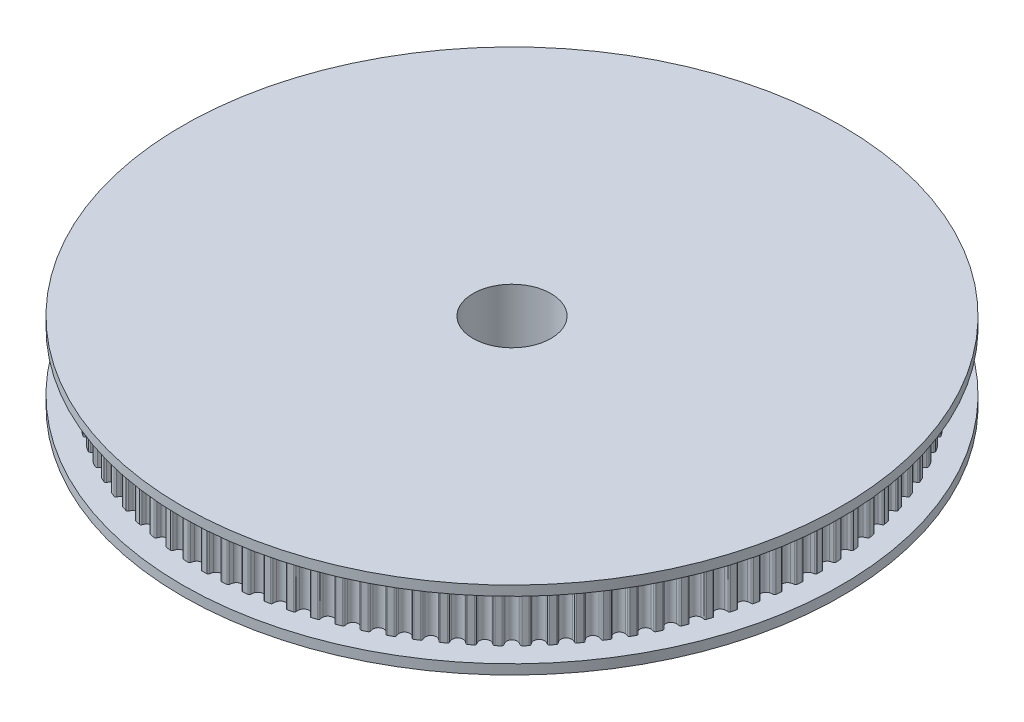
SolidWorks part; units mm, degrees
ref_plane "Front Plane" through (0, 0, 0) normal (0, 0, 1) x (1, 0, 0)
ref_plane "Top Plane" through (0, 0, 0) normal (0, 1, 0) x (1, 0, 0)
ref_plane "Right Plane" through (0, 0, 0) normal (1, 0, 0) x (0, 0, -1)
sketch "Sketch1" plane through (0, 0, 0) normal (0, 1, 0) x (1, 0, 0)
  circle A0 centre (0, 0) radius 31.831
  dimension "D1" = 63.662
extrude "Boss-Extrude1" add sketch "Sketch1" along normal mid plane 6
sketch "Sketch2" plane through (0, 0, 0) normal (0, 1, 0) x (1, 0, 0)
  line L0 (0, 0) -> (0, 31.577) construction
  line L1 (0, 0) -> (0.9857, 31.3665) construction
  line L2 (0, 31.577) -> (0, 31.831)
  line L3 (0.9857, 31.3665) -> (0.9998, 31.8153) construction
  line L4 (0.9998, 31.8153) -> (1.3996, 31.8002) construction
  line L5 (1.3996, 31.8002) -> (1.3902, 31.5521) construction
  line L6 (1.9827, 31.5147) -> (1.9987, 31.7682)
  arc A1 (0, 31.577) -> (0.2483, 31.576) centre (0, 0) cw
  arc A2 (0.2483, 31.576) -> (0.3962, 31.4425) centre (0.2471, 31.426) cw
  arc A3 (0.3962, 31.4425) -> (0.4813, 31.1351) centre (1.3902, 31.5521) ccw
  arc A4 (0.4813, 31.1351) -> (1.4746, 31.1038) centre (0.9857, 31.3665) ccw
  circle A5 centre (0, 0) radius 31.831 construction
  arc A6 (0, 31.831) -> (1.9987, 31.7682) centre (0, 0) cw
  arc A7 (1.5789, 31.4053) -> (1.4746, 31.1038) centre (0.5937, 31.5771) cw
  arc A8 (1.7349, 31.5293) -> (1.5789, 31.4053) centre (1.7266, 31.3795) ccw
  arc A9 (1.9827, 31.5147) -> (1.7349, 31.5293) centre (0, 0) ccw
  dimension "D2" = 0.15
  dimension "D3" = 1
  dimension "D4" = 0.555
  dimension "D1" = 1.8
  dimension "D5" = 0.254
  dimension "D6" = 0.4
  dimension "D7" = 1.004
extrude "Cut-Extrude1" cut sketch "Sketch2" against normal through all both and the other way through all
pattern_circular "CirPattern1" count 100 over 360 about axis through (0, 3, 0) along (0, -1, 0) of "Cut-Extrude1"
sketch "Sketch3" plane through (0, 0, 0) normal (0, 1, 0) x (1, 0, 0)
  circle A0 centre (0, 0) radius 33.831
  dimension "D1" = 67.662
extrude "Boss-Extrude2" add sketch "Sketch3" along normal blind 1 from surface starting at face at (0, 3, 0)
extrude "Boss-Extrude3" add sketch "Sketch3<2>" against normal blind 1 from surface starting at face at (0, -3, 0)
sketch "Sketch3<2>" plane through (0, 0, 0) normal (0, 1, 0) x (1, 0, 0) same geometry as "Sketch3"
sketch "Sketch4" plane through (0, 0, 0) normal (0, 1, 0) x (1, 0, 0)
  circle A0 centre (0, 0) radius 4
  dimension "D1" = 8
extrude "Cut-Extrude2" cut sketch "Sketch4" against normal through all both and the other way through all
equation "\"n\" = 100"
equation "\"p\"= 2mm"
equation "\"pd\"= ( \"n\" * \"p\" ) / pi"
equation "\"D1@Sketch1\"=\"pd\""
equation "\"D1@Sketch2\"=180/\"n\""
equation "\"D1@CirPattern1\"=\"n\""
equation "\"D1@Sketch3\"=\"pd\"+4mm"
